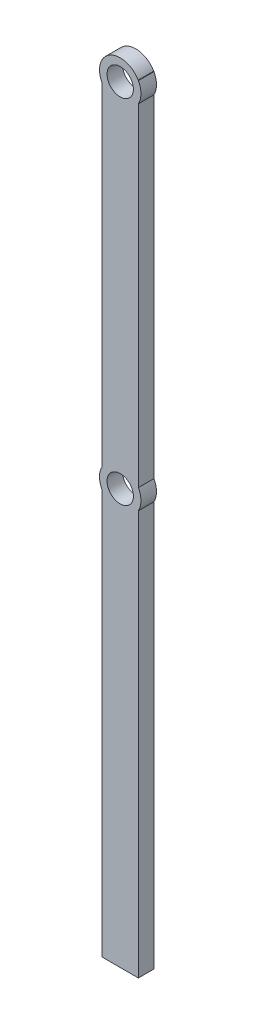
SolidWorks part; units mm, degrees
ref_plane "Front Plane" through (0, 0, 0) normal (0, 0, 1) x (1, 0, 0)
ref_plane "Top Plane" through (0, 0, 0) normal (0, 1, 0) x (1, 0, 0)
ref_plane "Right Plane" through (0, 0, 0) normal (1, 0, 0) x (0, 0, -1)
sketch "Sketch2" plane through (0, 0, 0) normal (0, 0, 1) x (1, 0, 0)
  circle A0 centre (0, 0) radius 12.7
  circle A1 centre (0, 0) radius 20
  dimension "D1" = 25.4
  dimension "D2" = 40
extrude "Boss-Extrude1" add sketch "Sketch2" along normal mid plane 15
sketch "Sketch4" plane through (0, 0, 0) normal (0, 1, 0) x (1, 0, 0)
  line L1 (-17.5, 7.5) -> (17.5, 7.5)
  line L2 (-17.5, 7.5) -> (-17.5, -7.5)
  line L3 (-17.5, -7.5) -> (17.5, -7.5)
  line L4 (17.5, 7.5) -> (17.5, -7.5)
  line L5 (-17.5, 7.5) -> (17.5, -7.5) construction
  line L6 (-17.5, -7.5) -> (17.5, 7.5) construction
  point P0 (0, 0)
  dimension "D1" = 35
  dimension "D2" = 15
extrude "Boss-Extrude2" add sketch "Sketch4" against normal blind 400
extrude "Boss-Extrude3" add sketch "Sketch4<2>" along normal blind 350
sketch "Sketch4<2>" plane through (0, 0, 0) normal (0, 1, 0) x (1, 0, 0) same geometry as "Sketch4"
sketch "Sketch5" plane through (0, 0, 0) normal (0, 0, 1) x (1, 0, 0)
  circle A0 centre (0, 0) radius 12.7
  dimension "D1" = 25.4
extrude "Cut-Extrude1" cut sketch "Sketch5" against normal through all both and the other way through all
pattern_linear "LPattern1" count 2 spacing 340 along (0, 1, 0) of "Boss-Extrude1", "Cut-Extrude1"
